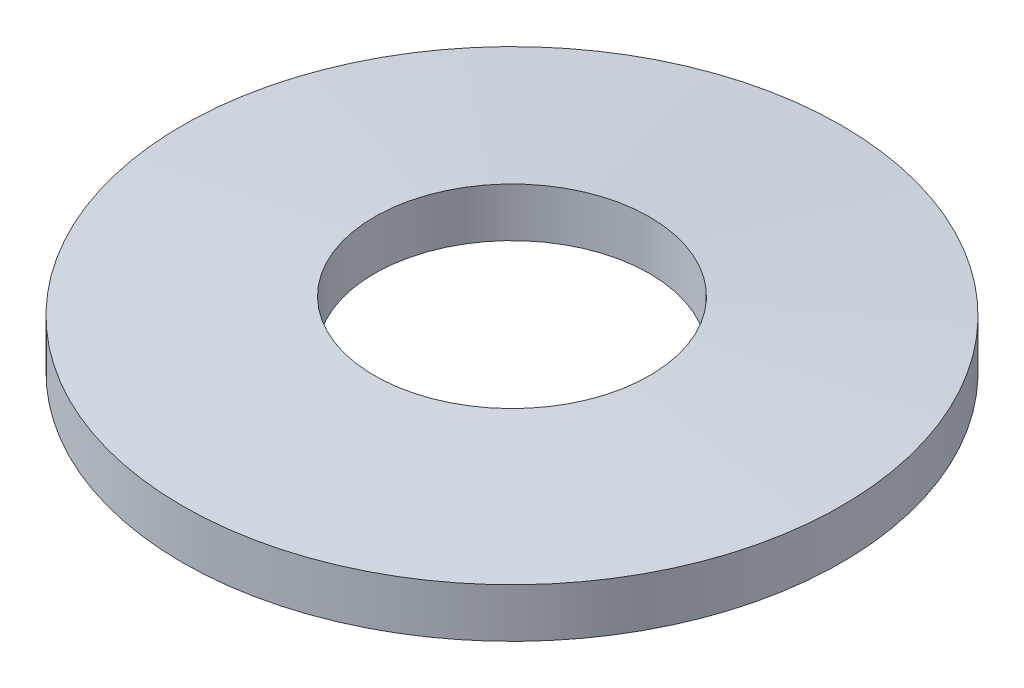
SolidWorks part; units mm, degrees
ref_plane "Front Plane" through (0, 0, 0) normal (0, 0, 1) x (1, 0, 0)
ref_plane "Top Plane" through (0, 0, 0) normal (0, 1, 0) x (1, 0, 0)
ref_plane "Right Plane" through (0, 0, 0) normal (1, 0, 0) x (0, 0, -1)
ref_axis "Axis1" through (0, 13.7354, 0) along (0, -1, 0)
sketch "Sketch1" plane through (0, 0, 0) normal (0, 0, 1) x (1, 0, 0)
  line L0 (2.5019, 1.1979) -> (2.5019, 0.3056)
  line L1 (2.5019, 0.3056) -> (5.9944, 0)
  line L4 (5.9944, 0) -> (5.9944, 0.8924)
  line L5 (5.9944, 0.8924) -> (2.5019, 1.1979)
  line L7 (0, 4.7341) -> (0, 8.8842) construction
  dimension "D1" = 5.0038
  dimension "D2" = 11.9888
  dimension "D3" = 0.889
  dimension "D4" = 85
revolve "Revolve1" add sketch "Sketch1" angle 360 about L7
